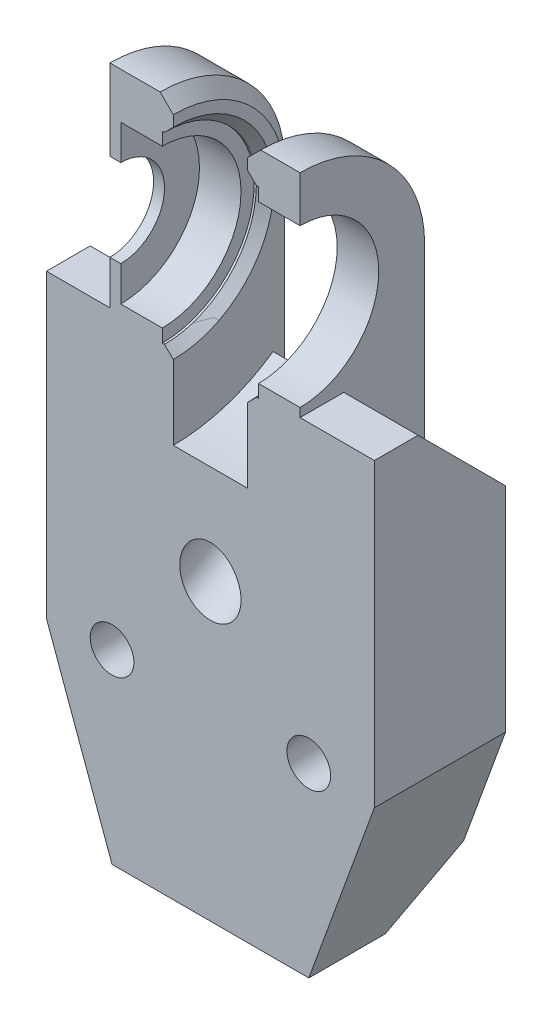
SolidWorks part; units mm, degrees
ref_plane "前视基准面" through (0, 0, 0) normal (0, 0, 1) x (1, 0, 0)
ref_plane "上视基准面" through (0, 0, 0) normal (0, 1, 0) x (1, 0, 0)
ref_plane "右视基准面" through (0, 0, 0) normal (1, 0, 0) x (0, 0, -1)
other "Configuration Table"
sketch "草图1" plane through (0, 0, 0) normal (0, 0, 1) x (1, 0, 0)
  line L1 (0, 0) -> (15, 0)
  line L2 (0, 0) -> (0, 23)
  line L3 (0, 23) -> (15, 23)
  line L4 (15, 0) -> (15, 23)
  dimension "D1" = 15
  dimension "D2" = 23
extrude "凸台-拉伸1" add sketch "草图1" along normal blind 12
ref_plane "基准面1" through (3.4, 0, 0) normal (-1, 0, 0) x (0, 0, 1)
sketch "草图2" plane through (3.4, 0, 0) normal (-1, 0, 0) x (0, 0, 1)
  line L0 (12, 23) -> (0, 23) construction
  line L1 (0.3, 23) -> (11.7, 23)
  line L2 (0.3, 23) -> (0.3, 27)
  line L4 (11.7, 23) -> (11.7, 27)
  line L5 (6, 27) -> (6, 23) construction
  arc A1 (11.7, 27) -> (0.3, 27) centre (6, 27) ccw
  circle A3 centre (6, 27) radius 3.6
  dimension "D2" = 4
  dimension "D3" = 7.2
  dimension "D1" = 11.4
extrude "凸台-拉伸2" add sketch "草图2" against normal blind 2.5
sketch "草图4" plane through (5.9, 0, 0) normal (1, 0, 0) x (0, 0, -1)
  circle A0 centre (-6, 27) radius 4.2
  circle M2 centre (-6, 27) radius 3.6
  line M6 (-11.7, 23) -> (-0.3, 23)
  dimension "D1" = 8.4
extrude "切除-拉伸1" cut sketch "草图4" against normal blind 0.6 and the other way blind 2.5 contours M2 | A0 M6 M2 | A0 M6 region at (5.9, 24.5932, 2.7023) region at (5.9, 22.9198, 6) region at (5.9, 27, 6)
chamfer "倒角1" distance 0.5 angle 45 1 edges at (5.9, 31.2, 6)
ref_plane "基准面2" through (7.5, 0, 0) normal (-1, 0, 0) x (0, 0, 1)
mirror "镜向1" about plane through (7.5, 0, 0) normal (-1, 0, 0) of "切除-拉伸1", "倒角1", "凸台-拉伸2"
sketch "草图5" plane through (7.5, 0, 0) normal (-1, 0, 0) x (0, 0, 1)
  arc A2 (2.8, 31) -> (15.2, 31) centre (9, 31) ccw
  circle A3 centre (9, 31) radius 8.2
  dimension "D1" = 2
extrude "切除-拉伸2" cut sketch "草图5" against normal mid plane 3.2 contours A3 region at (7.5, 31, 9)
sketch "草图6" plane through (3.4, 0, 0) normal (-1, 0, 0) x (0, 0, 1)
  line L3 (0.3, 27) -> (0.3, 23)
  line L4 (0.3, 23) -> (11.7, 23)
  line L5 (11.7, 23) -> (11.7, 27)
  line L6 (0.3, 27) -> (0.3, 23)
  line L7 (0.3, 23) -> (11.7, 23)
  line L8 (11.7, 23) -> (11.7, 27)
  line L9 (7, 28.7321) -> (7, 25.2679)
  circle A0 centre (6, 27) radius 3.6 construction
  arc A1 (11.7, 27) -> (0.3, 27) centre (6, 27) ccw
  arc A2 (11.7, 27) -> (0.3, 27) centre (6, 27) ccw
  circle A3 centre (6, 27) radius 3.6
  circle A6 centre (6, 27) radius 2
  point P11 (7, 27)
  circle M7 centre (6, 27) radius 3.6
  line M8 (0.3, 27) -> (0.3, 23)
  line M9 (0.3, 23) -> (11.7, 23)
  line M10 (11.7, 23) -> (11.7, 27)
  arc M11 (11.7, 27) -> (0.3, 27) centre (6, 27) ccw
  dimension "D3" = 4
  dimension "D2" = 1
  dimension "D1" = 0
extrude "凸台-拉伸3" add sketch "草图6" along normal blind 0.5 contours M11 M8 M9 M10 M7 | A6 M7 | L9 A6 region at (3.4, 32.5503, 6) region at (3.4, 27, 7.41) region at (3.4, 27, 2.5018)
sketch "草图7" plane through (0, 0, 0) normal (0, 0, -1) x (-1, 0, 0)
  line L0 (-15, 23) -> (0, 23) construction
  line L1 (-10.6, 23) -> (-4.4, 23)
  line L2 (-10.6, 23) -> (-10.6, 17.8)
  line L3 (-10.6, 17.8) -> (-4.4, 17.8)
  line L4 (-4.4, 23) -> (-4.4, 17.8)
  line L5 (-7.5, 0) -> (-7.5, 17.8) construction
  line L6 (0, 0) -> (-15, 0) construction
  dimension "D1" = 6.2
  dimension "D2" = 5.2
chamfer "倒角2" distance 4 angle 45 1 edges at (7.5, 23, 0)
ref_plane "基准面3" through (7.5, 0, 0) normal (-1, 0, 0) x (0, 0, 1)
sketch "草图15" plane through (7.5, 0, 0) normal (-1, 0, 0) x (0, 0, 1)
  line L0 (0.4645, 19.4645) -> (4.4645, 15.4645)
  line L1 (4, 23) -> (0, 19) construction
  line L2 (12, 14) -> (8, 14)
  line L3 (12, 0) -> (0, 0) construction
  line L4 (12, 23) -> (12, 0) construction
  line L5 (12, 23) -> (12, 0) construction
  arc A0 (8, 14) -> (4.4645, 15.4645) centre (8, 19) cw
  dimension "D2" = 14
  dimension "D1" = 5
  dimension "D3" = 4
sketch "草图40" plane through (0, 0, 12) normal (0, 0, 1) x (1, 0, 0)
  line L0 (5.9, 26) -> (5.9, 23)
  line L1 (15, 23) -> (0, 23) construction
  line L2 (5.9, 23) -> (5.9, 27) construction
  line L3 (5.9, 23) -> (0, 23)
  line L4 (0, 23) -> (2.9, 26)
  line L5 (2.9, 26) -> (5.9, 26)
  line L6 (2.9, 23) -> (2.9, 27) construction
  line L7 (5.9, 27) -> (2.9, 27) construction
  dimension "D1" = 1
extrude "凸台-拉伸4" add sketch "草图40" against normal up to surface (0.3 mm away) up to face at (4.4, 25, 11.7)
sketch "草图41" plane through (0, 0, 0) normal (-1, 0, 0) x (0, 0, 1)
  line L0 (11.7, 26) -> (7.85, 23)
  line L1 (11.7, 23) -> (4, 23) construction
  line L4 (11.7, 26) -> (11.7, 23)
  line L5 (11.7, 23) -> (12, 23)
  line L6 (12, 23) -> (12, 26)
  line L7 (12, 26) -> (11.7, 26)
  line L8 (11.7, 26) -> (11.7, 23)
  line L9 (11.7, 23) -> (12, 23)
  line L10 (12, 23) -> (12, 26)
  line L11 (12, 26) -> (11.7, 26)
  line M7 (12, 23) -> (11.7, 23)
  line M8 (11.7, 23) -> (4, 23)
  dimension "D1" = 0
extrude "凸台-拉伸5" add sketch "草图41" against normal blind 2.9 contours L8 L0 M8 | L10 L11 L8 M7 region at (0, 24, 10.4167) region at (0, 24.5, 11.85)
mirror "镜向3" about plane through (7.5, 0, 0) normal (-1, 0, 0) of "凸台-拉伸4", "凸台-拉伸5"
sketch "草图57" plane through (0, 0, 0) normal (0, 0, -1) x (-1, 0, 0)
  line L0 (-15, 9.5) -> (0, 9.5) construction
  line L2 (-7.5, 17.8076) -> (-7.5, 0) construction
  line L5 (0, 19) -> (-15, 19)
  line L6 (-15, 19) -> (-15, 0)
  line L7 (-15, 0) -> (0, 0)
  line L8 (0, 0) -> (0, 19)
  line L10 (0, 19) -> (-15, 19)
  line L11 (-15, 19) -> (-15, 0)
  line L12 (-15, 0) -> (0, 0)
  line L13 (0, 0) -> (0, 19)
  circle A0 centre (-12, 9.5) radius 1.7
  circle A1 centre (-3, 9.5) radius 1.7
  dimension "D2" = 3
  dimension "D3" = 3.4
  dimension "D1" = 0
extrude "切除-拉伸3" cut sketch "草图57" against normal blind 2 contours A0 | A1 region at (12, 9.5, 0) region at (3, 9.5, 0)
sketch "草图58" plane through (0, 0, 2) normal (0, 0, -1) x (-1, 0, 0)
  circle A0 centre (-12, 9.5) radius 1
  circle A1 centre (-3, 9.5) radius 1
  dimension "D1" = 2
extrude "切除-拉伸4" cut sketch "草图58" against normal up to next
sketch "草图59" plane through (0, 0, 12) normal (0, 0, 1) x (1, 0, 0)
  line L0 (15, 0) -> (15, 26) construction
  line L1 (3, 7.537) -> (4.7, 8.5185)
  line L2 (4.7, 8.5185) -> (4.7, 10.4815)
  line L3 (4.7, 10.4815) -> (3, 11.463)
  line L4 (3, 11.463) -> (1.3, 10.4815)
  line L5 (1.3, 10.4815) -> (1.3, 8.5185)
  line L6 (1.3, 8.5185) -> (3, 7.537)
  line L7 (12, 7.537) -> (13.7, 8.5185)
  line L8 (13.7, 8.5185) -> (13.7, 10.4815)
  line L9 (13.7, 10.4815) -> (12, 11.463)
  line L10 (12, 11.463) -> (10.3, 10.4815)
  line L11 (10.3, 10.4815) -> (10.3, 8.5185)
  line L12 (10.3, 8.5185) -> (12, 7.537)
  circle A0 centre (3, 9.5) radius 1.7 construction
  circle A1 centre (12, 9.5) radius 1.7 construction
  dimension "D1" = 3.4
extrude "切除-拉伸5" cut sketch "草图59" against normal blind 2 contours L2 L3 L4 L5 L6 L1 | L12 L7 L8 L9 L10 L11
sweep "切除-扫描1" cut path "草图15" circular profile diameter 2.8 parameters "D3"=2.8
sketch "草图79" plane through (7.5, 0, 0) normal (-1, 0, 0) x (0, 0, 1)
  arc A1 (-0.1177, 28.0068) -> (12.1941, 27.2693) centre (6, 27) ccw
  circle A2 centre (6, 27) radius 8
  dimension "D1" = 1.8
extrude "切除-拉伸7" cut sketch "草图79" against normal mid plane 3.2 contours A2 region at (7.5, 27, 6)
sketch "草图78" plane through (0, 0, 0) normal (-1, 0, 0) x (0, 0, 1)
  line L0 (6, 0) -> (6, 33.9991)
  line L1 (12, 0) -> (0, 0)
  line L2 (12, 0) -> (12, 33.9991)
  line L3 (12, 33.9991) -> (0, 33.9991)
  line L4 (0, 0) -> (0, 33.9991)
  line M1 (11.7, 26) -> (7.85, 23)
  line M2 (7.85, 23) -> (4, 23)
  line M5 (0, 0) -> (12, 0)
  line M6 (12, 0) -> (12, 26)
  line M7 (12, 26) -> (11.7, 26)
extrude "切除-拉伸6" cut sketch "草图78" against normal through all contours L0 M5 M6 M7 M1 M2 | L2 L3 L0 M2 M1 M7 region at (0, 12.0798, 9.0743) region at (0, 28.9983, 8.8188)
chamfer "倒角4" distance 0.7 angle 45 4 edges at (9.1, 23.15, 0.3) (9.1, 31.0305, 1.9695) (5.9, 31.0305, 1.9695) (5.9, 23.15, 0.3)
chamfer "倒角5" distance 0.5 angle 45 2 edges at (9.1, 22.8503, 5.3519) (5.9, 22.8503, 5.3519)
sketch "草图80" plane through (0, 0, 0) normal (0, -1, 0) x (1, 0, 0)
  line L4 (15, 6) -> (0, 6)
  line L5 (0, 6) -> (0, 0)
  line L6 (0, 0) -> (15, 0)
  line L7 (15, 0) -> (15, 6)
  line L8 (15, 6) -> (0, 6)
  line L9 (0, 6) -> (0, 0)
  line L10 (0, 0) -> (15, 0)
  line L11 (15, 0) -> (15, 6)
  dimension "D1" = 0
extrude "切除-拉伸8" cut sketch "草图80" against normal blind 1
chamfer "倒角8" distance 2.5 angle 50 1 edges at (7.5, 1, 0) first distance on face at (7.5, 1, 3)
chamfer "倒角9" distance 3 angle 70 1 edges at (0, 1, 4.25) first distance on face at (7.5, 1, 4.25)
chamfer "倒角10" distance 3 angle 70 1 edges at (15, 1, 4.25) first distance on face at (9, 1, 4.25)
sketch "草图83" plane through (5.9, 0, 0) normal (1, 0, 0) x (0, 0, -1)
  line L0 (-1, 20) -> (0.3482, 18.6518)
  line L1 (0.3482, 18.6518) -> (3.9013, 31.3634)
  line L2 (3.9013, 31.3634) -> (-1.6267, 34.3594)
  line L3 (-1.6267, 34.3594) -> (-6.2298, 34.1952)
  line L4 (-6, 22.3) -> (-6, 19)
  line L5 (-1.4322, 20.4322) -> (-1, 20)
  line L6 (-1, 20) -> (-1, 27)
  line L7 (-6, 32) -> (-6, 31.7)
  line L8 (-6, 22.3) -> (-6, 19)
  line L9 (-1.4322, 20.4322) -> (-1, 20)
  line L11 (-6, 32) -> (-6, 31.7)
  line L12 (-6.2298, 34.1952) -> (-6, 32)
  line L13 (-6, 31.7) -> (-6, 22.3)
  arc A4 (-3.8306, 22.8306) -> (-6, 31.7) centre (-6, 27) ccw
  arc A5 (-6, 22.3) -> (-3.8306, 22.8306) centre (-6, 27) ccw
  arc A6 (-6, 19) -> (-1.4322, 20.4322) centre (-6, 27) ccw
  arc A7 (-1, 27) -> (-6, 32) centre (-6, 27) ccw
  arc A9 (-6, 22.3) -> (-3.8306, 22.8306) centre (-6, 27) ccw
  arc A10 (-6, 19) -> (-1.4322, 20.4322) centre (-6, 27) ccw
  arc M14 (-6, 31.7) -> (-3.8306, 22.8306) centre (-6, 27) cw
  arc M15 (-3.8306, 22.8306) -> (-6, 22.3) centre (-6, 27) cw
  line M16 (-6, 22.3) -> (-6, 19)
  arc M17 (-6, 19) -> (-1.4322, 20.4322) centre (-6, 27) ccw
  line M18 (-1.4322, 20.4322) -> (-1, 20)
  line M19 (-1, 20) -> (-1, 27)
  arc M20 (-1, 27) -> (-6, 32) centre (-6, 27) ccw
  line M21 (-6, 32) -> (-6, 31.7)
  dimension "D1" = 0
extrude "切除-拉伸9" cut sketch "草图83" against normal blind 0.1 contours L3 L12 L0 L1 L2 M20 M19 | M21 M14 M15 M16 M17 M18 M19 M20 | L13 M14 M15 region at (5.9, 28.6401, 0.3027) region at (5.9, 22.5828, 3.1894) region at (5.9, 27, 4.0053)
sketch "草图84" plane through (9.1, 0, 0) normal (-1, 0, 0) x (0, 0, 1)
  line L0 (1, 20) -> (-0.1928, 18.8072)
  line L1 (6, 32) -> (7.2989, 33.6769)
  line L2 (7.2989, 33.6769) -> (-4.8689, 35.6628)
  line L3 (-4.8689, 35.6628) -> (-0.1928, 18.8072)
  line L4 (6, 19) -> (6, 22.3)
  line L5 (6, 31.7) -> (6, 32)
  line L6 (1, 27) -> (1, 20)
  line L7 (1, 20) -> (1.4322, 20.4322)
  line L8 (6, 19) -> (6, 22.3)
  line L9 (6, 31.7) -> (6, 32)
  line L11 (1, 20) -> (1.4322, 20.4322)
  line L12 (6, 22.2122) -> (6, 31.7)
  arc A4 (3.8306, 22.8306) -> (6, 22.3) centre (6, 27) ccw
  arc A5 (6, 31.7) -> (3.8306, 22.8306) centre (6, 27) ccw
  arc A6 (6, 32) -> (1, 27) centre (6, 27) ccw
  arc A7 (1.4322, 20.4322) -> (6, 19) centre (6, 27) ccw
  arc A8 (3.8306, 22.8306) -> (6, 22.3) centre (6, 27) ccw
  arc A11 (1.4322, 20.4322) -> (6, 19) centre (6, 27) ccw
  line M13 (6, 19) -> (6, 22.3)
  arc M14 (6, 22.3) -> (3.8306, 22.8306) centre (6, 27) cw
  arc M15 (3.8306, 22.8306) -> (6, 31.7) centre (6, 27) cw
  line M16 (6, 31.7) -> (6, 32)
  arc M17 (6, 32) -> (1, 27) centre (6, 27) ccw
  line M18 (1, 27) -> (1, 20)
  line M19 (1, 20) -> (1.4322, 20.4322)
  arc M20 (1.4322, 20.4322) -> (6, 19) centre (6, 27) ccw
  dimension "D1" = 0
extrude "切除-拉伸10" cut sketch "草图84" against normal blind 0.1 contours L2 L3 L0 L1 M18 M17 | L8 M20 M13 M14 M15 M16 M17 M18 M19 | L12 M14 M15 region at (9.1, 29.7808, -0.0122) region at (9.1, 22.5828, 3.1894) region at (9.1, 27, 4.0053)
